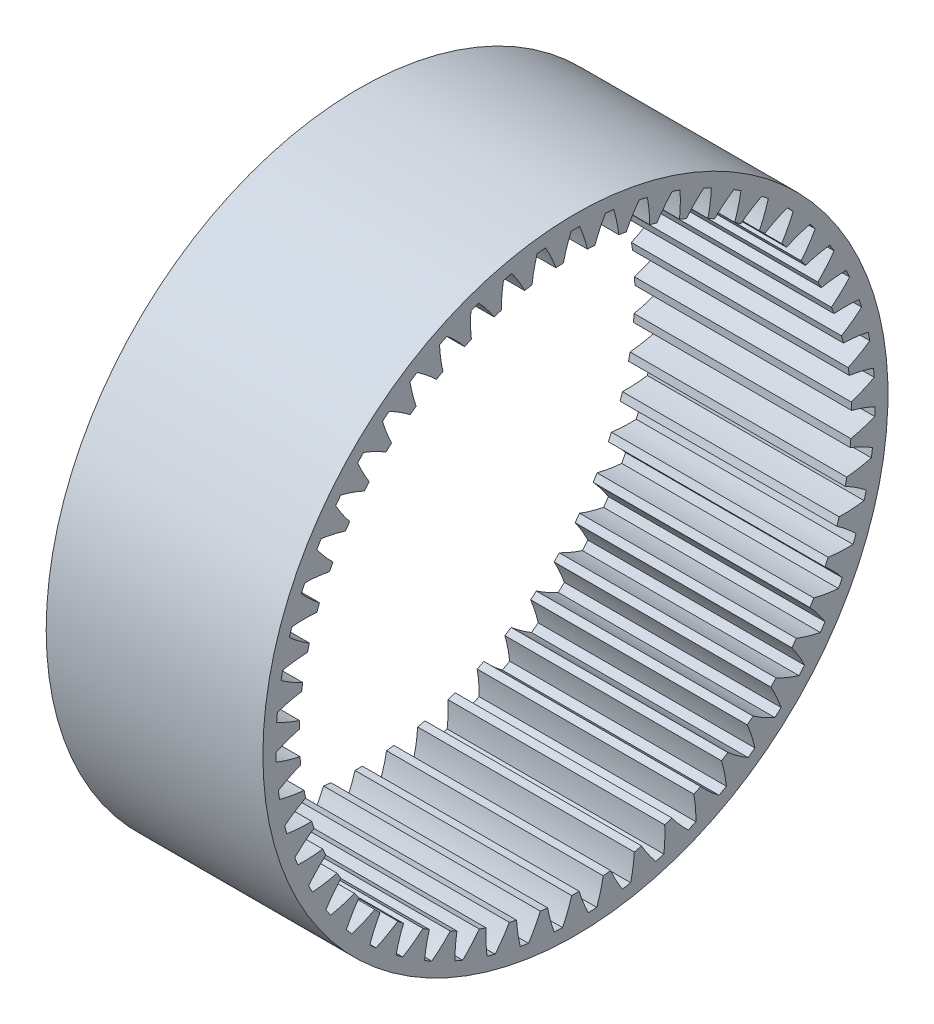
SolidWorks part; units mm, degrees
ref_plane "Plane1" through (0, 0, 0) normal (0, 0, 1) x (1, 0, 0)
ref_plane "Plane2" through (0, 0, 0) normal (0, 1, 0) x (1, 0, 0)
ref_plane "Plane3" through (0, 0, 0) normal (1, 0, 0) x (0, 0, -1)
sketch "HoldingSke" plane through (0, 0, 0) normal (0, 1, 0) x (1, 0, 0)
  line L0 (0, 0) -> (0.4589, -0.6553)
  line L1 (-15, 0) -> (100, 0) construction
  line L2 (0, 0) -> (-2.1039, 2.3779)
  line L3 (0, 0) -> (-11.863, 4.5341)
  line L4 (0, 0) -> (4.9534, 7.0742)
  line L5 (0, 0) -> (-23.7986, -8.8762)
  line L6 (0, 0) -> (-10.5278, -7.1032)
  line L7 (-2.1039, 2.3779) -> (3.3635, 27.1825)
  line L8 (-76.2, 3.6279) -> (-54.61, 3.6279)
  line L9 (-67.7845, 28.3722) -> (-49.3413, 33.142)
  line L10 (-76.2, 71.12) -> (104.1128, 71.12)
  line L11 (0, 0) -> (-26, 0)
  line L12 (-76.2, 101.6) -> (-76.155, 101.6)
  line L13 (24.9733, 27.94) -> (52.9518, 28.4284)
  line L14 (24.9733, 27.94) -> (24.9743, 27.94)
  line L15 (24.9733, 27.94) -> (100.4006, 29.5858)
  circle A0 centre (0, 0) radius 37.5
  circle A1 centre (0, 0) radius 12.7
  circle A2 centre (0, 0) radius 12.7
  dimension "Num_teeth" = 55
  dimension "Pitch_radius" = 180.3128
  dimension "Width" = 26
  dimension "Diameter" = 75
sketch "BasProSke" plane through (0, 0, 0) normal (0, 1, 0) x (1, 0, 0)
  line L0 (-10, 0) -> (60, 0) construction
  line L1 (0, 33.125) -> (0, 37.5)
  line L2 (0, 33.125) -> (26, 33.125)
  line L3 (26, 33.125) -> (26, 37.5)
  line L4 (26, 37.5) -> (0, 37.5)
  dimension "Thickness" = 26
  dimension "Diameter" = 75
revolve "Base-Revolve" add sketch "BasProSke" angle 360 about L0
sketch "TooCutSke" plane through (0, 0, 0) normal (1, 0, 0) x (0, 0, -1)
  line L3 (1.0941, 34.3576) -> (1.0941, 53.6633) construction
  line L4 (0, 0) -> (0, 59.563) construction
  line L5 (0, 0) -> (-3.9007, 68.2161) construction
  line L6 (-15.2783, 29.1274) -> (36.0712, 32.0636) construction
  circle A0 centre (0, 0) radius 34.375 construction
  circle A1 centre (0, 0) radius 35.9385 construction
  circle A2 centre (0, 0) radius 29.9521 construction
  circle A3 centre (0, 0) radius 33.0996 construction
  arc A4 (1.4514, 33.0678) -> (0.5036, 35.935) centre (-15.2783, 29.1274) ccw
  arc A5 (1.4514, 33.0678) -> (-1.4514, 33.0678) centre (0, 0) ccw
  arc A6 (0.5036, 35.935) -> (-0.5036, 35.935) centre (0, 0) ccw
  arc A7 (-0.5036, 35.935) -> (-1.4514, 33.0678) centre (15.2783, 29.1274) ccw
extrude "ToothCut" cut sketch "TooCutSke" along normal through all
fillet "Breaks" [suppressed] radius 0.125
fillet "RootFillets" [suppressed] radius 0.3135
pattern_circular "TeethCuts" count 55 every 6.545 about axis through (-10, 0, 0) along (1, 0, 0) of "RootFillets", "Breaks", "ToothCut"
equation "' \"Module@HoldingSke\" = 6.35"
equation "' \"Num_teeth@HoldingSke\" = 24"
equation "' \"Ap@HoldingSke\" =  14.5"
equation "' \"Ap@HoldingSke\" = 14.5"
equation "' \"Width@HoldingSke\" = 12"
equation "' \"Diameter@HoldingSke\" = 8 * 25.4"
equation "' \"Show_teeth@HoldingSke\" = 100"
equation "' \"Backlash@HoldingSke\" = 0.009 * 25.4"
equation "' \"Addendum_fac@HoldingSke\" = 1.0"
equation "' \"Dedendum_fac@HoldingSke\" = 1.25"
equation "' \"Dedendum_add@HoldingSke\" = 0.00005 * 25.4"
equation "' \"Clearance_fac@HoldingSke\" = 0.25"
equation "\"Pitch@HoldingSke\" = 1 / \"Module@HoldingSke\" "
equation "\"Overcut_dia@TooCutSke\" = (\"Num_teeth@HoldingSke\" - 2 * \"Addendum_fac@HoldingSke\") / \"Pitch@HoldingSke\" - 0.002 * 25.4"
equation "\"Pitch_dia@TooCutSke\" = \"Num_teeth@HoldingSke\" / \"Pitch@HoldingSke\""
equation "\"Base_dia@TooCutSke\" = \"Num_teeth@HoldingSke\" / \"Pitch@HoldingSke\" * cos((\"Ap@HoldingSke\"  * 3.14159265 / 180)) * 0.90"
equation "\"Root_dia@TooCutSke\" = \"Num_teeth@HoldingSke\"  / \"Pitch@HoldingSke\" + 2 *  \"Dedendum_fac@HoldingSke\"/ \"Pitch@HoldingSke\" + \"Dedendum_add@HoldingSke\" * 2"
equation "\"Half_ang@TooCutSke\" = 180 / \"Num_teeth@HoldingSke\""
equation "\"Half_CT@TooCutSke\" = \"Num_teeth@HoldingSke\" / \"Pitch@HoldingSke\" * sin((3.14159265 / 2 / \"Num_teeth@HoldingSke\")) / 2 + 10 * \"Backlash@HoldingSke\" / 4"
equation "\"Flank_rad@TooCutSke\" = \"Num_teeth@HoldingSke\" / \"Pitch@HoldingSke\" / 4"
equation "\"Radius@RootFillets\"= \"Clearance_fac@HoldingSke\" / \"Pitch@HoldingSke\" + \"Dedendum_add@HoldingSke\""
equation "\"Break_rad@Breaks\" = 0.02 / \"Pitch@HoldingSke\" * 5"
equation "\"Num_teeth@TeethCuts\" = int( \"Show_teeth@HoldingSke\" ) + 1"
equation "\"Num_teeth@TeethCuts\" = ((sgn( \"Num_teeth@TeethCuts\" - \"Num_teeth@HoldingSke\" )-1)*( \"Num_teeth@TeethCuts\" - \"Num_teeth@HoldingSke\" ))/-2+ \"Num_teeth@HoldingSke\""
equation "\"Num_teeth@TeethCuts\" = ((sgn( \"Num_teeth@TeethCuts\" - 2.0)+1)*( \"Num_teeth@TeethCuts\" - 2.0))/2 +2.0"
equation "\"Angle@TeethCuts\" = 360.0 / \"Num_teeth@HoldingSke\""
equation "\"Diameter@BasProSke\" = \"Num_teeth@HoldingSke\"  / \"Pitch@HoldingSke\" + 2 *  \"Dedendum_fac@HoldingSke\"/ \"Pitch@HoldingSke\" + \"Dedendum_add@HoldingSke\" * 2 + 0.002 * 25.4"
equation "\"Diameter@BasProSke\" = ((sgn( \"Diameter@BasProSke\"  - \"Diameter@HoldingSke\" )+1)*( \"Diameter@BasProSke\"  - \"Diameter@HoldingSke\" ))/2 + \"Diameter@HoldingSke\""
equation "\"Inside_diameter@BasProSke\" =  (\"Num_teeth@HoldingSke\" - 2 * \"Addendum_fac@HoldingSke\") / \"Pitch@HoldingSke\" "
equation "\"Thickness@BasProSke\"  = \"Width@HoldingSke\""
